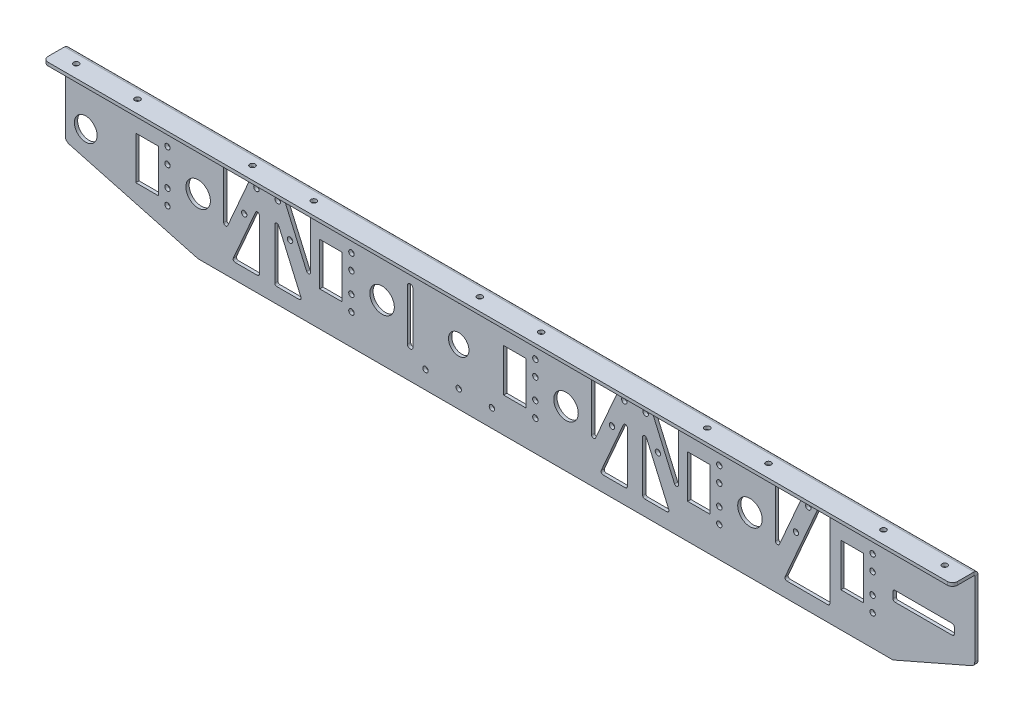
SolidWorks part; units mm, degrees
note: The reader was unsure of these and kept them because the rebuilt part matched: flange length of "Outward Edge-Flange".
material "5052-H32"
ref_plane "Front Plane" through (0, 0, 0) normal (0, 0, 1) x (1, 0, 0)
ref_plane "Top Plane" through (0, 0, 0) normal (0, 1, 0) x (1, 0, 0)
ref_plane "Right Plane" through (0, 0, 0) normal (1, 0, 0) x (0, 0, -1)
sketch "Sketch1" plane through (0, 0, 0) normal (0, 0, 1) x (1, 0, 0)
  line L0 (-30, 25) -> (100, 25) construction
  line L5 (-30, 25) -> (-30, -25) construction
  line L6 (70.7107, -70.7107) -> (0, 0) construction
  line L7 (-50, 10) -> (120, 10) construction
  line L8 (-50, 10) -> (-50, -10) construction
  line L9 (-50, -10) -> (120, -10) construction
  line L10 (120, 10) -> (120, -10) construction
  line L11 (0, 0) -> (100, 0) construction
  line L12 (250.7107, -70.7107) -> (180, 0) construction
  line L13 (120, -20) -> (140, -20) construction
  line L14 (120, -20) -> (120, 20) construction
  line L15 (120, 20) -> (140, 20) construction
  line L16 (140, -20) -> (140, 20) construction
  line L17 (430.7107, -70.7107) -> (360, 0) construction
  line L18 (610.7107, -70.7107) -> (540, 0) construction
  line L20 (680, 5.01) -> (740, 5.01)
  line L21 (680, 5.01) -> (680, -5.01)
  line L22 (680, -5.01) -> (740, -5.01)
  line L23 (0, 0) -> (80.7856, -58.938) construction
  line L24 (-28.8068, 0) -> (730, 0) construction
  line L25 (-130, 60) -> (760, 60)
  line L27 (0, -55) -> (680, -55)
  line L28 (760, -20) -> (680, -55)
  line L29 (0, -55) -> (-130, -20)
  line L31 (-130, -20) -> (-130, 60)
  line L32 (760, 60) -> (760, -20)
  line L33 (740, 5.01) -> (740, -5.01)
  line L34 (-60, 40) -> (0, 0) construction
  circle A0 centre (0, 0) radius 11.9875
  circle A1 centre (-30, 25) radius 2.5 construction
  circle A3 centre (-30, -25) radius 2.5 construction
  circle A5 centre (-50, 10) radius 2.5 construction
  circle A6 centre (-50, -10) radius 2.5 construction
  circle A9 centre (100, 0) radius 40 construction
  arc A10 (100, 0) -> (70.7107, -70.7107) centre (0, 0) cw construction
  circle A11 centre (70.7107, -70.7107) radius 40 construction
  circle A12 centre (180, 0) radius 11.9875
  circle A13 centre (150, 25) radius 2.5 construction
  circle A14 centre (130, 10) radius 2.5 construction
  circle A15 centre (130, -10) radius 2.5 construction
  circle A16 centre (150, -25) radius 2.5 construction
  circle A17 centre (360, 0) radius 11.9875
  circle A18 centre (330, 25) radius 2.5 construction
  circle A19 centre (310, 10) radius 2.5 construction
  circle A20 centre (310, -10) radius 2.5 construction
  circle A21 centre (330, -25) radius 2.5 construction
  circle A22 centre (540, 0) radius 11.9875
  circle A23 centre (510, 25) radius 2.5 construction
  circle A24 centre (490, 10) radius 2.5 construction
  circle A25 centre (490, -10) radius 2.5 construction
  circle A26 centre (510, -25) radius 2.5 construction
  circle A27 centre (0, 0) radius 17.5 construction
  circle A28 centre (250.7107, -70.7107) radius 40 construction
  circle A29 centre (430.7107, -70.7107) radius 40 construction
  circle A30 centre (610.7107, -70.7107) radius 40 construction
  circle A31 centre (-60, 40) radius 11 construction
  circle A34 centre (730, 0) radius 40 construction
  circle A35 centre (660, 25) radius 2.5 construction
  circle A36 centre (640, 10) radius 2.5 construction
  circle A37 centre (640, -10) radius 2.5 construction
  circle A38 centre (660, -25) radius 2.5 construction
  circle A42 centre (-110, 0) radius 11.1125
  circle A43 centre (-110, 0) radius 40 construction
  circle A44 centre (-30, 10) radius 2.5 construction
  circle A45 centre (-30, -10) radius 2.5 construction
  circle A46 centre (150, -10) radius 2.5 construction
  circle A47 centre (150, 10) radius 2.5 construction
  circle A48 centre (330, -10) radius 2.5 construction
  circle A49 centre (330, 10) radius 2.5 construction
  circle A50 centre (510, -10) radius 2.5 construction
  circle A51 centre (510, 10) radius 2.5 construction
  circle A52 centre (660, 10) radius 2.5 construction
  circle A53 centre (660, -10) radius 2.5 construction
  point P12 (130, 20)
  point P20 (-50, 0)
  point P28 (-30, 0)
  point P66 (120, 0)
  point P96 (680, 0)
  dimension "D1" = 23.975
  dimension "D6" = 50
  dimension "D7" = 5
  dimension "D2" = 170
  dimension "D9" = 4
  dimension "D11" = 80
  dimension "D12" = 100
  dimension "D17" = 540
  dimension "D20" = 35
  dimension "D5" = 22
  dimension "D26" = 20
  dimension "D34" = 150
  dimension "D15" = 20
  dimension "D21" = 110
  dimension "D22" = 22.225
  dimension "D23" = 60
  dimension "D3" = 20
  dimension "D4" = 130
  dimension "D8" = 30
  dimension "D10" = 20
  dimension "D13" = 45
  dimension "D14" = 60
  dimension "D16" = 60.7107
  dimension "D18" = 40
  dimension "D19" = 20
  dimension "D24" = 40
  dimension "D25" = 8.887
  dimension "D27" = 190
  dimension "D28" = 60
  dimension "D29" = 30
  dimension "D30" = 50
  dimension "D31" = 30
  dimension "D32" = 70
  dimension "D33" = 2
  dimension "D35" = 10.02
base flange "Base-Flange1" sketch "Sketch1" thickness 3.175 reverse thickness direction no parameters "D1"=0.7366
edge flange "Inward Edge-Flange" [suppressed] sketch "Sketch6" flange angle 90 flange position material inside bend radius 0.7366 thickness 3.175
sketch "Sketch6" plane through (0, 60, -3.175) normal (0, 1, 0) x (1, 0, 0)
  line L2 (-130, 0) -> (-130, 21.825)
  line L3 (-130, 21.825) -> (760, 21.825)
  line L4 (760, 21.825) -> (760, 0)
  line L9 (760, 0) -> (-130, 0) construction
  line L10 (760, 0) -> (-130, 0)
bend "EdgeBend1" bend radius 0.7366 bend angle 90 parameters "D5"=1, "D6"=10, "D7"=25
sketch "Inward Hole-Pattern" [suppressed] plane through (0, 60, 0) normal (0, 1, 0) x (1, 0, 0)
  line L0 (-130, 25) -> (-130, 0)
  line L2 (315, 25) -> (315, 0)
  line L3 (760, 0) -> (-130, 0) construction
  line L4 (-110, 12.5) -> (-50, 12.5) construction
  line L5 (62.5, 12.5) -> (122.5, 12.5) construction
  line L6 (-130, 25) -> (315, 25)
  circle A0 centre (-110, 12.5) radius 2.5 construction
  circle A1 centre (-50, 12.5) radius 2.5 construction
  circle A2 centre (285, 12.5) radius 2.5 construction
  circle A6 centre (62.5, 12.5) radius 2.5 construction
  circle A7 centre (122.5, 12.5) radius 2.5 construction
  circle A8 centre (345, 12.5) radius 2.5 construction
  circle A9 centre (507.5, 12.5) radius 2.5 construction
  circle A10 centre (567.5, 12.5) radius 2.5 construction
  circle A11 centre (680, 12.5) radius 2.5 construction
  circle A12 centre (740, 12.5) radius 2.5 construction
  point P4 (-130, 12.5)
  point P10 (92.5, 25)
  point P27 (92.5, 12.5)
  dimension "D1" = 5
  dimension "D2" = 20
  dimension "D3" = 30
  dimension "50" = 60
hole_wizard "Inward M5 Clearance Hole0" [suppressed] positions "3DSketch3" profile "Sketch18" hole size "M5" standard "ANSI Metric"
sketch3d "3DSketch3" [suppressed]
  point P0 (-110, 60, -12.5)
  point P2 (-50, 60, -12.5)
  point P4 (285, 60, -12.5)
  point P26 (62.5, 60, -12.5)
  point P28 (122.5, 60, -12.5)
  point P35 (345, 60, -12.5)
  point P37 (507.5, 60, -12.5)
  point P39 (567.5, 60, -12.5)
  point P41 (680, 60, -12.5)
  point P52 (740, 60, -12.5)
sketch "Sketch18" plane through (-110, 60, -12.5) normal (1, 0, 0) x (0, 0, 1)
  line L0 (0, 0) -> (0, 3.175)
  line L1 (0, 3.175) -> (2.65, 3.175)
  line L2 (2.65, 3.175) -> (2.65, 0)
  line L5 (2.65, 0) -> (0, 0)
  line L11 (0, -6.35) -> (0, 107.95) construction
  dimension "Thru Hole Dia." = 5.3
  dimension "Thru Hole Depth" = 3.175
hole_wizard "M5 Clearance Hole1" positions "3DSketch1" profile "Sketch7" hole size "M5" standard "ANSI Metric" end condition up to next
sketch3d "3DSketch1"
  point P0 (-50, 10, 0)
  point P2 (-50, -10, 0)
  point P4 (-30, -25, 0)
  point P6 (-30, 25, 0)
  point P17 (130, 10, 0)
  point P19 (130, -10, 0)
  point P21 (150, -25, 0)
  point P23 (150, 25, 0)
  point P25 (310, 10, 0)
  point P27 (310, -10, 0)
  point P29 (330, -25, 0)
  point P31 (330, 25, 0)
  point P33 (490, 10, 0)
  point P35 (490, -10, 0)
  point P37 (510, -25, 0)
  point P39 (510, 25, 0)
  point P66 (640, 10, 0)
  point P68 (640, -10, 0)
  point P71 (660, 25, 0)
  point P73 (660, -25, 0)
  point P84 (-30, 10, 0)
  point P86 (-30, -10, 0)
  point P88 (150, 10, 0)
  point P90 (150, -10, 0)
  point P92 (330, 10, 0)
  point P94 (330, -10, 0)
  point P96 (510, 10, 0)
  point P98 (510, -10, 0)
  point P117 (660, 10, 0)
  point P119 (660, -10, 0)
sketch "Sketch7" plane through (-50, 10, 0) normal (1, 0, 0) x (0, -1, 0)
  line L0 (0, 0) -> (0, 3.175)
  line L1 (0, 3.175) -> (2.65, 3.175)
  line L2 (2.65, 3.175) -> (2.65, 0)
  line L5 (2.65, 0) -> (0, 0)
  line L11 (0, -6.35) -> (0, 107.95) construction
  dimension "Thru Hole Dia." = 5.3
  dimension "Thru Hole Depth" = 3.175
sketch "Sketch9" plane through (0, 0, 0) normal (0, 0, 1) x (1, 0, 0)
  line L0 (-50, 10) -> (-50, -10)
  line L1 (-61, 21) -> (-39, 21)
  line L2 (-61, 21) -> (-61, -21)
  line L3 (-61, -21) -> (-39, -21)
  line L4 (-39, 21) -> (-39, -21)
  line L5 (-30, 25) -> (-30, -25)
  line L6 (119, 21) -> (119, -21)
  line L7 (119, 21) -> (141, 21)
  line L8 (141, 21) -> (141, -21)
  line L9 (119, -21) -> (141, -21)
  line L10 (299, 21) -> (299, -21)
  line L11 (299, 21) -> (321, 21)
  line L12 (321, 21) -> (321, -21)
  line L13 (299, -21) -> (321, -21)
  line L14 (479, 21) -> (479, -21)
  line L15 (479, 21) -> (501, 21)
  line L16 (501, 21) -> (501, -21)
  line L17 (479, -21) -> (501, -21)
  line L22 (659, 21) -> (659, -21) [skipped]
  line L23 (659, -21) -> (681, -21) [skipped]
  line L24 (681, 21) -> (681, -21) [skipped]
  line L25 (659, 21) -> (681, 21) [skipped]
  line L26 (629, 21) -> (629, -21)
  line L27 (629, -21) -> (651, -21)
  line L28 (651, 21) -> (651, -21)
  line L29 (629, 21) -> (651, 21)
  circle A0 centre (-30, 10) radius 2.65
  circle A1 centre (-30, -10) radius 2.65
  circle A2 centre (-30, -25) radius 2.65 construction
  circle A3 centre (150, 10) radius 2.65
  circle A4 centre (150, -10) radius 2.65
  circle A5 centre (330, 10) radius 2.65
  circle A6 centre (330, -10) radius 2.65
  circle A7 centre (510, 10) radius 2.65
  circle A8 centre (510, -10) radius 2.65
  circle A11 centre (690, 10) radius 2.65 [skipped]
  circle A12 centre (690, -10) radius 2.65 [skipped]
  circle A13 centre (660, 10) radius 2.65
  circle A14 centre (660, -10) radius 2.65
  point P9 (-50, 21)
  point P10 (-61, 0)
  point P11 (-50, 0)
  dimension "D1" = 22
  dimension "D2" = 42
  dimension "D4" = 540
  dimension "D6" = 150
  dimension "D3" = 5
  dimension "D5" = 2
extrude "Inner Plate Cut-Extrude3" cut sketch "Sketch9" against normal up to next (3.175 mm away)
sketch "Sketch8" plane through (0, 0, 0) normal (0, 0, 1) x (1, 0, 0)
  line L0 (0, 0) -> (180, 0) construction
  line L1 (180, 0) -> (360, 0) construction
  line L2 (360, 0) -> (540, 0) construction
  line L3 (540, 0) -> (760, 0) construction
  line L4 (60, 21.2883) -> (33.1864, -40)
  line L5 (25, 40) -> (110, 40) construction
  line L6 (25, 40) -> (25, -40) construction
  line L7 (25, -40) -> (110, -40) construction
  line L8 (110, 40) -> (110, -40) construction
  line L9 (60, 40) -> (75, 40) construction
  line L10 (60, 40) -> (60, -40) construction
  line L11 (60, -40) -> (75, -40) construction
  line L12 (75, 40) -> (75, -40) construction
  line L13 (51.8136, 40) -> (25, -21.2883)
  line L14 (67.5, 40) -> (67.5, -40)
  line L15 (25, -40) -> (60, 40)
  line L16 (75, 21.2883) -> (101.8136, -40)
  line L17 (83.1864, 40) -> (110, -21.2883)
  line L18 (83.1864, 40) -> (110, 40)
  line L19 (110, 40) -> (110, -21.2883)
  line L20 (51.8136, 40) -> (25, 40)
  line L21 (25, 40) -> (25, -21.2883)
  line L22 (60, 21.2883) -> (60, -40)
  line L23 (60, -40) -> (33.1864, -40)
  line L24 (101.8136, -40) -> (75, -40)
  line L25 (75, -40) -> (75, 21.2883)
  line L26 (290, 40) -> (290, -21.2883)
  line L27 (263.1864, 40) -> (290, -21.2883)
  line L28 (263.1864, 40) -> (290, 40)
  line L29 (255, -40) -> (255, 21.2883)
  line L30 (255, 21.2883) -> (281.8136, -40)
  line L31 (281.8136, -40) -> (255, -40)
  line L32 (240, -40) -> (213.1864, -40)
  line L33 (240, 21.2883) -> (213.1864, -40)
  line L34 (240, 21.2883) -> (240, -40)
  line L35 (205, 40) -> (205, -21.2883)
  line L36 (231.8136, 40) -> (205, -21.2883)
  line L37 (231.8136, 40) -> (205, 40)
  line L38 (470, 40) -> (470, -21.2883)
  line L39 (443.1864, 40) -> (470, -21.2883)
  line L40 (443.1864, 40) -> (470, 40)
  line L41 (435, -40) -> (435, 21.2883)
  line L42 (435, 21.2883) -> (461.8136, -40)
  line L43 (461.8136, -40) -> (435, -40)
  line L44 (420, -40) -> (393.1864, -40)
  line L45 (420, 21.2883) -> (393.1864, -40)
  line L46 (420, 21.2883) -> (420, -40)
  line L47 (385, 40) -> (385, -21.2883)
  line L48 (411.8136, 40) -> (385, -21.2883)
  line L49 (411.8136, 40) -> (385, 40)
  line L56 (600, -40) -> (573.1864, -40)
  line L57 (600, 21.2883) -> (573.1864, -40)
  line L58 (600, 21.2883) -> (600, -40)
  line L59 (565, 40) -> (565, -21.2883)
  line L60 (591.8136, 40) -> (565, -21.2883)
  line L61 (591.8136, 40) -> (565, 40)
  line L62 (615, -40) -> (615, 21.2883) [skipped]
  line L63 (615, 21.2883) -> (641.8136, -40) [skipped]
  line L64 (641.8136, -40) -> (615, -40) [skipped]
  line L65 (650, 40) -> (650, -21.2883) [skipped]
  line L66 (623.1864, 40) -> (650, -21.2883) [skipped]
  line L67 (623.1864, 40) -> (650, 40) [skipped]
  line L68 (760, -20) -> (760, 60) construction
  line L69 (600, -40) -> (618.1864, -40)
  line L70 (618.1864, -40) -> (618.1864, 40)
  line L71 (618.1864, 40) -> (608.1864, 40)
  line L72 (608.1864, 40) -> (600, 21.2883)
  line L73 (0, 0) -> (81.9152, -57.3576) construction
  line L74 (0, 0) -> (10.0376, 14.3352) construction
  line L75 (10.0376, 14.3352) -> (91.9528, -43.0225) construction
  line L76 (91.9528, -43.0225) -> (81.9152, -57.3576) construction
  circle A0 centre (150, 25) radius 2.65 construction
  circle A1 centre (81.9152, -57.3576) radius 40 construction
  circle A2 centre (45.0409, 5.8079) radius 2.65
  circle A3 centre (57.0655, 33.2926) radius 2.65
  circle A6 centre (225.0409, 5.8079) radius 2.65
  circle A7 centre (237.0655, 33.2926) radius 2.65
  circle A8 centre (405.0409, 5.8079) radius 2.65
  circle A9 centre (417.0655, 33.2926) radius 2.65
  circle A10 centre (585.0409, 5.8079) radius 2.65
  circle A11 centre (597.0655, 33.2926) radius 2.65
  circle A12 centre (89.9591, 5.8079) radius 2.65
  circle A13 centre (77.9345, 33.2926) radius 2.65
  circle A14 centre (269.9591, 5.8079) radius 2.65
  circle A15 centre (257.9345, 33.2926) radius 2.65
  circle A16 centre (449.9591, 5.8079) radius 2.65
  circle A17 centre (437.9345, 33.2926) radius 2.65
  circle A20 centre (617.9345, 33.2926) radius 2.65 [skipped]
  circle A21 centre (629.9591, 5.8079) radius 2.65 [skipped]
  point P16 (25, 0)
  point P23 (67.5, 40)
  point P24 (67.5, 40)
  dimension "D10" = 80
  dimension "D12" = 30
  dimension "D13" = 50
  dimension "D14" = 5.3
  dimension "D1" = 25
  dimension "D2" = 40
  dimension "D3" = 80
  dimension "D4" = 15
  dimension "D5" = 15
  dimension "D7" = 540
  dimension "D8" = 45
  dimension "D9" = 100
  dimension "D11" = 35
  dimension "D15" = 17.5
  dimension "D6" = 4
extrude "Swiss Cheese Cutout" cut sketch "Sketch8" against normal up to next (3.175 mm away) contours L20 L21 L13 | L23 L22 L4 | L25 L24 L16 | L19 L18 L17 | L36 L37 L35 | L34 L33 L32 | L31 L30 L29 | L28 L27 L26 | L48 L49 L47 | L46 L45 L44 | L43 L42 L41 | L40 L39 L38 | L60 L61 L59 | L58 L57 L56 | L71 L72 L58 L69 L70 | A6 | A7 | A8 | A9 | A10 | A11 | A13 | A12 | A15 | A14 | A17 | A16 | A2 | A3
fillet "Fillet1" radius 2 47 edges at (110, -21.2883, -1.5875) (101.8136, -40, -1.5875) (75, -40, -1.5875) (75, 21.2883, -1.5875) (83.1864, 40, -1.5875) (110, 40, -1.5875) (60, 21.2883, -1.5875) (60, -40, -1.5875) (33.1864, -40, -1.5875) (25, -21.2883, -1.5875) (51.8136, 40, -1.5875) (25, 40, -1.5875) (740, -5.01, -1.5875) (740, 5.01, -1.5875) (680, -5.01, -1.5875) (680, 5.01, -1.5875) (618.1864, -40, -1.5875) (573.1864, -40, -1.5875) (565, -21.2883, -1.5875) (591.8136, 40, -1.5875) (565, 40, -1.5875) (608.1864, 40, -1.5875) (618.1864, 40, -1.5875) (411.8136, 40, -1.5875) (420, 21.2883, -1.5875) (435, 21.2883, -1.5875) (393.1864, -40, -1.5875) (461.8136, -40, -1.5875) (435, -40, -1.5875) (385, -21.2883, -1.5875) (385, 40, -1.5875) (443.1864, 40, -1.5875) (470, 40, -1.5875) (470, -21.2883, -1.5875) (420, -40, -1.5875) (240, -40, -1.5875) (255, -40, -1.5875) (281.8136, -40, -1.5875) (213.1864, -40, -1.5875) (240, 21.2883, -1.5875) (255, 21.2883, -1.5875) (290, -21.2883, -1.5875) (263.1864, 40, -1.5875) (290, 40, -1.5875) (231.8136, 40, -1.5875) (205, 40, -1.5875) (205, -21.2883, -1.5875)
fillet "Fillet2" [suppressed] radius 5
edge flange "Outward Edge-Flange" sketch "Sketch12" flange angle 90 flange length 25 flange position material inside bend radius 0.7366 thickness 3.175 parameters "D6"=10
sketch "Sketch12" plane through (0, 60, 0) normal (0, 1, 0) x (-1, 0, 0)
  line L2 (-760, 0) -> (-760, 21.825)
  line L3 (-760, 21.825) -> (130, 21.825)
  line L4 (130, 21.825) -> (130, 0)
  line L6 (-760, 0) -> (130, 0) construction
  line L7 (-760, 0) -> (130, 0)
bend "EdgeBend2" [suppressed] bend radius 0.7366 bend angle 90 parameters "D5"=1
sketch "Outward Hole-Pattern" plane through (0, 60, -60) normal (0, -1, 0) x (1, 0, 0)
  line L0 (-130, 81.825) -> (-130, 56.825)
  line L2 (315, 81.825) -> (315, 56.825)
  line L4 (-110, 69.325) -> (-50, 69.325) construction
  line L5 (62.5, 69.325) -> (122.5, 69.325) construction
  line L6 (-130, 81.825) -> (315, 81.825)
  line L7 (-130, 81.825) -> (760, 81.825) construction
  circle A0 centre (-110, 69.325) radius 2.5 construction
  circle A1 centre (-50, 69.325) radius 2.5 construction
  circle A2 centre (285, 69.325) radius 2.5 construction
  circle A6 centre (62.5, 69.325) radius 2.5 construction
  circle A7 centre (122.5, 69.325) radius 2.5 construction
  circle A8 centre (345, 69.325) radius 2.5 construction
  circle A9 centre (507.5, 69.325) radius 2.5 construction
  circle A10 centre (567.5, 69.325) radius 2.5 construction
  circle A11 centre (680, 69.325) radius 2.5 construction
  circle A12 centre (740, 69.325) radius 2.5 construction
  point P4 (-130, 69.325)
  point P10 (92.5, 81.825)
  point P27 (92.5, 69.325)
  dimension "D1" = 5
  dimension "D2" = 20
  dimension "D3" = 30
  dimension "50" = 60
hole_wizard "Outward M5 Clearance Hole4" positions "3DSketch5" profile "Sketch22" hole size "M5" standard "ANSI Metric" end condition up to next
sketch3d "3DSketch5"
  point P0 (-110, 60, 9.325)
  point P2 (-50, 60, 9.325)
  point P9 (62.5, 60, 9.325)
  point P11 (122.5, 60, 9.325)
  point P13 (285, 60, 9.325)
  point P15 (345, 60, 9.325)
  point P17 (507.5, 60, 9.325)
  point P19 (567.5, 60, 9.325)
  point P21 (680, 60, 9.325)
  point P23 (740, 60, 9.325)
sketch "Sketch22" plane through (-110, 60, 9.325) normal (1, 0, 0) x (0, 0, 1)
  line L0 (0, 0) -> (0, 3.175)
  line L1 (0, 3.175) -> (2.65, 3.175)
  line L2 (2.65, 3.175) -> (2.65, 0)
  line L5 (2.65, 0) -> (0, 0)
  line L11 (0, -6.35) -> (0, 107.95) construction
  dimension "Thru Hole Dia." = 5.3
  dimension "Thru Hole Depth" = 3.175
fillet "Fillet3" radius 5 6 edges at (760, 58.4125, 21.825) (760, -20, -1.5875) (680, -55, -1.5875) (0, -55, -1.5875) (-130, -20, -1.5875) (-130, 58.4125, 21.825)
sketch "Sketch13" plane through (0, 0, 0) normal (0, 0, 1) x (1, 0, 0)
  line L0 (266.2444, 40) -> (288, 40) construction
  line L1 (205, 40) -> (290, 40)
  line L2 (205, 40) -> (205, -40)
  line L3 (205, -40) -> (290, -40)
  line L4 (290, 40) -> (290, -40)
  line L5 (278.7556, -40) -> (257, -40) construction
  line L6 (290, 38) -> (290, -11.7271) construction
  line L7 (205, 38) -> (205, -11.7271) construction
extrude "Inner Plate Swiss Cheese Fill" add sketch "Sketch13" against normal blind 3.175
sketch "Sketch14" plane through (0, 0, 0) normal (0, 0, 1) x (1, 0, 0)
  line L0 (204.85, 25) -> (204.85, -25)
  line L1 (210.15, 25) -> (210.15, -25)
  line L2 (299, 21) -> (321, 21) construction
  line L3 (299, 21) -> (321, 21) construction
  line L4 (299, 21) -> (299, -21) construction
  line L5 (299, -21) -> (321, -21) construction
  line L6 (321, 21) -> (321, -21) construction
  line L7 (299, 21) -> (299, -21) construction
  line L8 (222.5, 37.5) -> (287.5, 37.5) construction
  line L9 (222.5, 37.5) -> (222.5, -37.5) construction
  line L10 (222.5, -37.5) -> (287.5, -37.5) construction
  line L11 (287.5, 37.5) -> (287.5, -37.5) construction
  circle A2 centre (255, 0) radius 10
  circle A5 centre (255, 37.5) radius 2.5 construction
  circle A7 centre (255, -37.5) radius 2.5 construction
  arc A8 (204.85, 25) -> (210.15, 25) centre (207.5, 25) cw
  arc A9 (210.15, -25) -> (204.85, -25) centre (207.5, -25) cw
  circle A10 centre (255, 0) radius 31.5 construction
  circle A11 centre (180, 0) radius 11.9875 construction
  circle A12 centre (180, 0) radius 11.9875 construction
  circle A15 centre (180, 0) radius 40 construction
  circle A19 centre (222.5, 37.5) radius 2.5 construction
  circle A20 centre (287.5, 37.5) radius 2.5 construction
  circle A21 centre (287.5, -37.5) radius 2.5 construction
  circle A22 centre (222.5, -37.5) radius 2.5 construction
  point P1 (222.5, 0)
  point P2 (255, 37.5)
  point P21 (204.85, 0)
  point P24 (255, 0)
  point P45 (255, 0)
  dimension "D1" = 20
  dimension "D2" = 50
  dimension "D3" = 2.65
  dimension "D4" = 75
  dimension "D6" = 63
  dimension "D10" = 80
  dimension "D12" = 5
  dimension "D5" = 15
  dimension "D8" = 75
  dimension "D13" = 65
extrude "Inner Plate Motor Mount" cut sketch "Sketch14" against normal up to next
hole_wizard "Inner Plate Motor M5 Clearance Holes" positions "3DSketch2" profile "Sketch15" hole size "M5" standard "ANSI Metric"
sketch3d "3DSketch2"
  point P60 (222.5, 37.5, 0)
  point P62 (287.5, 37.5, 0)
  point P64 (287.5, -37.5, 0)
  point P66 (222.5, -37.5, 0)
  point P77 (255, 37.5, 0)
  point P79 (255, -37.5, 0)
sketch "Sketch15" plane through (222.5, 37.5, 0) normal (1, 0, 0) x (0, -1, 0)
  line L0 (0, 0) -> (0, 6.5923)
  line L1 (0, 6.5923) -> (2.65, 5)
  line L2 (2.65, 5) -> (2.65, 0)
  line L5 (2.65, 0) -> (0, 0)
  line L10 (0, 6.5923) -> (-2.65, 5) construction
  line L11 (0, -6.35) -> (0, 107.95) construction
  dimension "Hole Dia." = 5.3
  dimension "Hole Depth" = 5
  dimension "Drill Angle" = 118
sketch "Bend-Lines1" [suppressed] plane through (0, 0, 0) normal (0, 1, 0) x (1, 0, 0)
sketch "Bounding-Box1" [suppressed] plane through (0, 0, 0) normal (0, 1, 0) x (1, 0, 0)
sheet metal parameters "Sheet-Metal8" thickness 3.175 parameters "D1"=0.7366
flat pattern "Flat-Pattern8" [suppressed]
sketch "Bend-Lines2" plane through (0, 0, 0) normal (0, 1, 0) x (1, 0, 0)
sketch3d "Bounding-Box2" [suppressed]
  line L0 (-120, -55, 0) -> (870, -55, 0) construction
  line L1 (-120, 50, 0) -> (870, 50, 0) construction
  line L2 (-120, -55, 0) -> (-120, 50, 0) construction
  line L3 (870, -55, 0) -> (870, 50, 0) construction
sheet metal parameters "Sheet-Metal9" thickness 3.175 parameters "D1"=0.7366
flat pattern "Flat-Pattern8" [suppressed]
sketch "Bend-Lines2" plane through (0, 0, 0) normal (0, 0, 1) x (1, 0, 0)
  line L0 (760, 57.9137) -> (-130, 57.9137) construction
  line L1 (760, 57.9137) -> (-130, 57.9137) construction
sketch3d "Bounding-Box2" [suppressed]
  line L0 (-130, -55, 0) -> (760, -55, 0) construction
  line L1 (-130, 80.8275, 0) -> (760, 80.8275, 0) construction
  line L2 (-130, -55, 0) -> (-130, 80.8275, 0) construction
  line L3 (760, -55, 0) -> (760, 80.8275, 0) construction
bend of the flat pattern "Flatten-<EdgeBend1>1"
sketch "Sketch16-1" [suppressed] plane through (0, 55.8275, 0) normal (0, 0, 1) x (1, 0, 0)
  circle A0 centre (-114.3999, 14.4355) radius 8.3052
  circle A1 centre (-73.982, 14.4355) radius 5.4058
sheet metal parameters "Sheet-Metal10" thickness 3.175 parameters "D1"=0.7366
flat pattern "Flat-Pattern8" [suppressed]
sketch "Bend-Lines2" plane through (0, 0, 0) normal (0, 0, 1) x (1, 0, 0)
  line L0 (780, 57.9137) -> (-130, 57.9137) construction
  line L1 (780, 57.9137) -> (-130, 57.9137) construction
sketch3d "Bounding-Box2" [suppressed]
  line L0 (-130, -55, 0) -> (780, -55, 0) construction
  line L1 (-130, 70.8275, 0) -> (780, 70.8275, 0) construction
  line L2 (-130, -55, 0) -> (-130, 70.8275, 0) construction
  line L3 (780, -55, 0) -> (780, 70.8275, 0) construction
bend of the flat pattern "Flatten-<EdgeBend1>3"
sheet metal parameters "Sheet-Metal11" thickness 3.175 parameters "D1"=0.7366
flat pattern "Flat-Pattern8" [suppressed]
sketch "Bend-Lines2" plane through (0, 0, 0) normal (0, 0, 1) x (1, 0, 0)
  line L0 (760, 57.9137) -> (-130, 57.9137) construction
  line L1 (760, 57.9137) -> (-130, 57.9137) construction
sketch3d "Bounding-Box2" [suppressed]
  line L0 (-130, -55, 0) -> (760, -55, 0) construction
  line L1 (-130, 80.8275, 0) -> (760, 80.8275, 0) construction
  line L2 (-130, -55, 0) -> (-130, 80.8275, 0) construction
  line L3 (760, -55, 0) -> (760, 80.8275, 0) construction
sketch "Sketch16-4" plane through (0, 55.8275, 0) normal (0, 0, 1) x (1, 0, 0)
  line L0 (-130, 25) -> (-130, 0)
  line L2 (315, 25) -> (315, 0)
  line L4 (-110, 12.5) -> (-50, 12.5) construction
  line L5 (62.5, 12.5) -> (122.5, 12.5) construction
  line L6 (-130, 25) -> (315, 25)
  circle A0 centre (-110, 12.5) radius 2.5 construction
  circle A1 centre (-50, 12.5) radius 2.5 construction
  circle A2 centre (285, 12.5) radius 2.5 construction
  circle A6 centre (62.5, 12.5) radius 2.5 construction
  circle A7 centre (122.5, 12.5) radius 2.5 construction
  circle A8 centre (345, 12.5) radius 2.5 construction
  circle A9 centre (507.5, 12.5) radius 2.5 construction
  circle A10 centre (567.5, 12.5) radius 2.5 construction
  circle A11 centre (680, 12.5) radius 2.5 construction
  circle A12 centre (740, 12.5) radius 2.5 construction
  dimension "D1" = 5
  dimension "D2" = 20
  dimension "D3" = 30
  dimension "50" = 60
sheet metal parameters "Sheet-Metal13" thickness 3.175 parameters "D1"=0.7366
flat pattern "Flat-Pattern8"
sketch "Bend-Lines2" plane through (0, 0, 0) normal (0, 0, 1) x (1, 0, 0)
  line L0 (780, 57.9137) -> (-130, 57.9137) construction
  line L1 (780, 57.9137) -> (-130, 57.9137) construction
sketch3d "Bounding-Box2" [suppressed]
  line L0 (-130, -55, 0) -> (780, -55, 0) construction
  line L1 (-130, 70.8275, 0) -> (780, 70.8275, 0) construction
  line L2 (-130, -55, 0) -> (-130, 70.8275, 0) construction
  line L3 (780, -55, 0) -> (780, 70.8275, 0) construction
sheet metal parameters "Sheet-Metal14" thickness 3.175 parameters "D1"=0.7366
flat pattern "Flat-Pattern8"
sketch "Bend-Lines2" plane through (0, 0, 0) normal (0, 0, 1) x (1, 0, 0)
sketch3d "Bounding-Box2" [suppressed]
  line L0 (-130, -55, 0) -> (780, -55, 0) construction
  line L1 (-130, 70.8275, 0) -> (780, 70.8275, 0) construction
  line L2 (-130, -55, 0) -> (-130, 70.8275, 0) construction
  line L3 (780, -55, 0) -> (780, 70.8275, 0) construction
bend of the flat pattern "Flatten-<EdgeBend2>1"
sheet metal parameters "Sheet-Metal15" thickness 3.175 parameters "D1"=0.7366
flat pattern "Flat-Pattern8" [suppressed]
sketch "Bend-Lines2" plane through (0, 0, 0) normal (0, 0, 1) x (1, 0, 0)
sketch3d "Bounding-Box2" [suppressed]
  line L0 (-130, -55, 0) -> (780, -55, 0) construction
  line L1 (-130, 70.8275, 0) -> (780, 70.8275, 0) construction
  line L2 (-130, -55, 0) -> (-130, 70.8275, 0) construction
  line L3 (780, -55, 0) -> (780, 70.8275, 0) construction
bend of the flat pattern "Flatten-<EdgeBend2>2"
sheet metal parameters "Sheet-Metal16" thickness 3.175 parameters "D1"=0.7366
flat pattern "Flat-Pattern8" [suppressed]
sketch "Bend-Lines2" plane through (0, 0, 0) normal (0, 0, 1) x (1, 0, 0)
sketch3d "Bounding-Box2" [suppressed]
  line L0 (-130, -55, 0) -> (780, -55, 0) construction
  line L1 (-130, 70.8275, 0) -> (780, 70.8275, 0) construction
  line L2 (-130, -55, 0) -> (-130, 70.8275, 0) construction
  line L3 (780, -55, 0) -> (780, 70.8275, 0) construction
bend of the flat pattern "Flatten-<EdgeBend2>3"
sheet metal parameters "Sheet-Metal17" thickness 3.175 parameters "D1"=0.7366
flat pattern "Flat-Pattern8" [suppressed]
sketch "Bend-Lines2" plane through (0, 0, 0) normal (0, 0, 1) x (1, 0, 0)
sketch3d "Bounding-Box2" [suppressed]
  line L0 (-130, -55, 0) -> (760, -55, 0) construction
  line L1 (-130, 80.8275, 0) -> (760, 80.8275, 0) construction
  line L2 (-130, -55, 0) -> (-130, 80.8275, 0) construction
  line L3 (760, -55, 0) -> (760, 80.8275, 0) construction
bend of the flat pattern "Flatten-<EdgeBend2>4"
sketch "Sketch20-2" plane through (0, 60, -60) normal (0, -1, 0) x (1, 0, 0)
  line L0 (-130, 81.825) -> (-130, 56.825)
  line L2 (315, 81.825) -> (315, 56.825)
  line L4 (-110, 69.325) -> (-50, 69.325) construction
  line L5 (62.5, 69.325) -> (122.5, 69.325) construction
  line L6 (-130, 81.825) -> (315, 81.825)
  circle A0 centre (-110, 69.325) radius 2.5 construction
  circle A1 centre (-50, 69.325) radius 2.5 construction
  circle A2 centre (285, 69.325) radius 2.5 construction
  circle A6 centre (62.5, 69.325) radius 2.5 construction
  circle A7 centre (122.5, 69.325) radius 2.5 construction
  circle A8 centre (345, 69.325) radius 2.5 construction
  circle A9 centre (507.5, 69.325) radius 2.5 construction
  circle A10 centre (567.5, 69.325) radius 2.5 construction
  circle A11 centre (680, 69.325) radius 2.5 construction
  circle A12 centre (740, 69.325) radius 2.5 construction
  dimension "D1" = 5
  dimension "D2" = 20
  dimension "D3" = 30
  dimension "50" = 60
sketch "Sketch16-3" plane through (0, 55.8275, 0) normal (0, 0, 1) x (1, 0, 0)
  line L0 (-130, 25) -> (-130, 0)
  line L2 (315, 25) -> (315, 0)
  line L4 (-110, 12.5) -> (-50, 12.5) construction
  line L5 (62.5, 12.5) -> (122.5, 12.5) construction
  line L6 (-130, 25) -> (315, 25)
  circle A0 centre (-110, 12.5) radius 2.5 construction
  circle A1 centre (-50, 12.5) radius 2.5 construction
  circle A2 centre (285, 12.5) radius 2.5 construction
  circle A6 centre (62.5, 12.5) radius 2.5 construction
  circle A7 centre (122.5, 12.5) radius 2.5 construction
  circle A8 centre (345, 12.5) radius 2.5 construction
  circle A9 centre (507.5, 12.5) radius 2.5 construction
  circle A10 centre (567.5, 12.5) radius 2.5 construction
  circle A11 centre (680, 12.5) radius 2.5 construction
  circle A12 centre (740, 12.5) radius 2.5 construction
  dimension "D1" = 5
  dimension "D2" = 20
  dimension "D3" = 30
  dimension "50" = 60
sheet metal parameters "Sheet-Metal18" thickness 3.175 parameters "D1"=0.7366
flat pattern "Flat-Pattern8" [suppressed]
sketch "Bend-Lines2" plane through (0, 0, 0) normal (0, 0, 1) x (1, 0, 0)
  line L0 (760, 57.9137) -> (-130, 57.9137) construction
  line L1 (760, 57.9137) -> (-130, 57.9137) construction
sketch3d "Bounding-Box2" [suppressed]
  line L0 (-130, -55, 0) -> (760, -55, 0) construction
  line L1 (-130, 80.8275, 0) -> (760, 80.8275, 0) construction
  line L2 (-130, -55, 0) -> (-130, 80.8275, 0) construction
  line L3 (760, -55, 0) -> (760, 80.8275, 0) construction
bend of the flat pattern "Flatten-<EdgeBend1>1"
sketch "Sketch16-1" plane through (0, 55.8275, 0) normal (0, 0, 1) x (1, 0, 0)
  line L0 (-130, 25) -> (-130, 0)
  line L1 (-130, 25) -> (760, 25)
  line L2 (315, 25) -> (315, 0)
  circle A0 centre (-110, 12.5) radius 2.5 construction
  circle A1 centre (-50, 12.5) radius 2.5 construction
  circle A2 centre (285, 12.5) radius 2.5 construction
  circle A3 centre (345, 12.5) radius 2.5 construction
  circle A4 centre (680, 12.5) radius 2.5 construction
  circle A5 centre (740, 12.5) radius 2.5 construction
  dimension "D1" = 5
  dimension "D2" = 20
  dimension "D3" = 30
  dimension "50" = 60
sheet metal parameters "Sheet-Metal19" thickness 3.175 parameters "D1"=0.7366
flat pattern "Flat-Pattern8" [suppressed]
sketch "Bend-Lines2" plane through (0, 0, 0) normal (0, 0, 1) x (1, 0, 0)
sketch3d "Bounding-Box2" [suppressed]
  line L0 (-130, -55, 0) -> (780, -55, 0) construction
  line L1 (-130, 70.8275, 0) -> (780, 70.8275, 0) construction
  line L2 (-130, -55, 0) -> (-130, 70.8275, 0) construction
  line L3 (780, -55, 0) -> (780, 70.8275, 0) construction
bend of the flat pattern "Flatten-<EdgeBend2>1"
sketch "Sketch20-1" [suppressed] plane through (0, 60, -60) normal (0, -1, 0) x (1, 0, 0)
  line L0 (-130, 81.825) -> (-130, 56.825)
  line L2 (315, 81.825) -> (315, 56.825)
  line L4 (-110, 69.325) -> (-50, 69.325) construction
  line L5 (62.5, 69.325) -> (122.5, 69.325) construction
  line L6 (-130, 81.825) -> (315, 81.825)
  circle A0 centre (-110, 69.325) radius 2.5 construction
  circle A1 centre (-50, 69.325) radius 2.5 construction
  circle A2 centre (285, 69.325) radius 2.5 construction
  circle A6 centre (62.5, 69.325) radius 2.5 construction
  circle A7 centre (122.5, 69.325) radius 2.5 construction
  circle A8 centre (345, 69.325) radius 2.5 construction
  circle A9 centre (507.5, 69.325) radius 2.5 construction
  circle A10 centre (567.5, 69.325) radius 2.5 construction
  circle A11 centre (680, 69.325) radius 2.5 construction
  circle A12 centre (740, 69.325) radius 2.5 construction
  dimension "D1" = 5
  dimension "D2" = 20
  dimension "D3" = 30
  dimension "50" = 60
